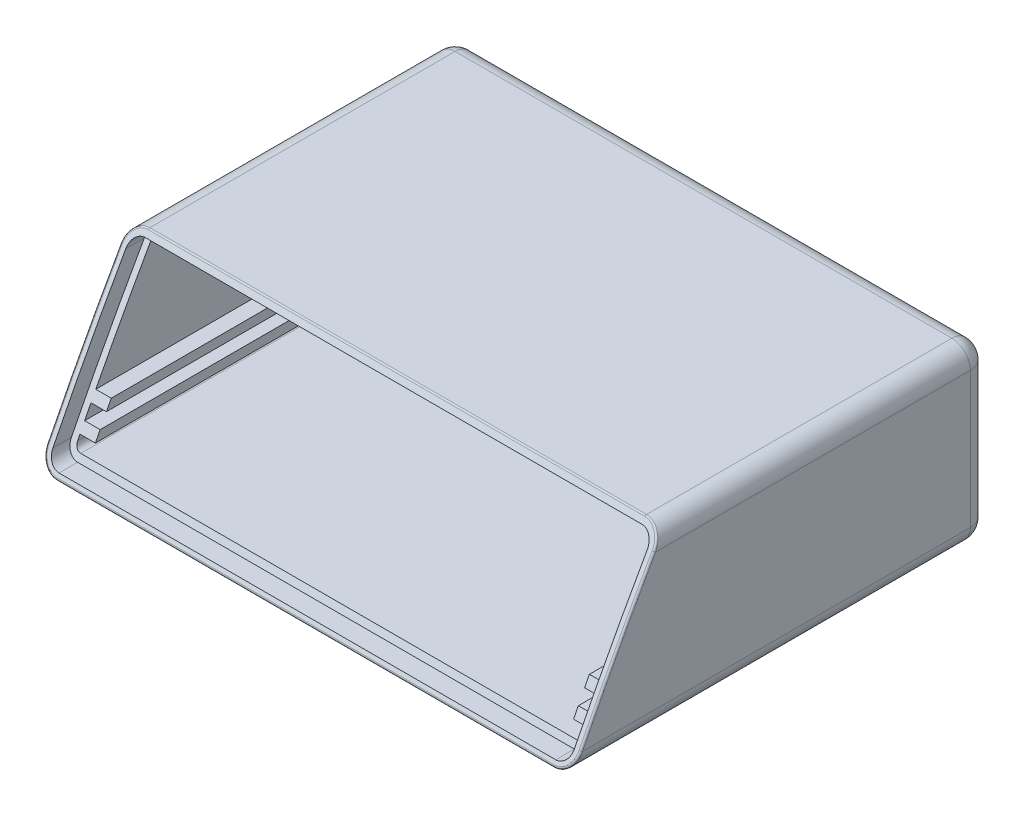
SolidWorks part; units mm, degrees
ref_plane "Front Plane" through (0, 0, 0) normal (0, 0, 1) x (1, 0, 0)
ref_plane "Top Plane" through (0, 0, 0) normal (0, 1, 0) x (1, 0, 0)
ref_plane "Right Plane" through (0, 0, 0) normal (1, 0, 0) x (0, 0, -1)
sketch "Sketch1" plane through (0, 0, 0) normal (0, 1, 0) x (1, 0, 0)
  line L1 (-43.14, -33.75) -> (43.14, -33.75)
  line L2 (-43.14, -33.75) -> (-43.14, 33.75)
  line L3 (-43.14, 33.75) -> (43.14, 33.75)
  line L4 (43.14, -33.75) -> (43.14, 33.75)
  line L5 (-43.14, -33.75) -> (43.14, 33.75) construction
  line L6 (-43.14, 33.75) -> (43.14, -33.75) construction
  point P0 (0, 0)
  dimension "D1" = 67.5
  dimension "D2" = 86.28
extrude "Boss-Extrude1" add sketch "Sketch1" along normal blind 28
fillet "Fillet1" radius 3 4 edges at (43.14, 28, 0) (43.14, 0, 0) (-43.14, 0, 0) (-43.14, 28, 0)
shell "Shell1" thickness 2
sketch "Sketch2" plane through (-43.14, 0, 0) normal (-1, 0, 0) x (0, 0, 1)
  line L0 (-33.75, 28) -> (33.75, 28) construction
  line L1 (18.75, 28) -> (33.75, 28)
  line L2 (33.75, 28) -> (33.75, 0)
  arc A0 (33.75, 0) -> (18.75, 28) centre (-392.2189, -210.1797) ccw
  dimension "D1" = 15
  dimension "D2" = 475
extrude "Cut-Extrude1" cut sketch "Sketch2" against normal through all
sketch "Sketch3" plane through (0, 0, -33.75) normal (0, 0, -1) x (-1, 0, 0)
  line L0 (-7.15, 18.7) -> (7.15, 18.7)
  line L1 (-6.95, 18.5) -> (6.95, 18.5) construction
  line L2 (-6.95, 18.5) -> (-6.95, 2.2) construction
  line L3 (-6.95, 2.2) -> (6.95, 2.2) construction
  line L4 (6.95, 18.5) -> (6.95, 2.2) construction
  line L5 (7.15, 18.7) -> (7.15, 2)
  line L6 (-7.15, 2) -> (7.15, 2)
  line L7 (-7.15, 18.7) -> (-7.15, 2)
  line L8 (27.25, 17.2) -> (38.3, 17.2)
  line L9 (27.45, 17) -> (38.1, 17) construction
  line L10 (27.45, 17) -> (27.45, 3.35) construction
  line L11 (27.45, 3.35) -> (38.1, 3.35) construction
  line L12 (38.1, 17) -> (38.1, 3.35) construction
  line L13 (38.3, 17.2) -> (38.3, 3.15)
  line L14 (27.25, 3.15) -> (38.3, 3.15)
  line L15 (27.25, 17.2) -> (27.25, 3.15)
  dimension "D1" = 0.2
  dimension "D2" = 0.2
extrude "Cut-Extrude2" cut sketch "Sketch3" against normal up to surface (2 mm away) up to face at (0, 14, -31.75)
fillet "Fillet2" radius 3 8 edges at (42.2613, 27.1213, -33.75) (43.14, 14, -33.75) (42.2613, 0.8787, -33.75) (0, 0, -33.75) (-42.2613, 0.8787, -33.75) (-43.14, 14, -33.75) (-42.2613, 27.1213, -33.75) (0, 28, -33.75)
sketch "Sketch4" plane through (0, 0, -31.75) normal (0, 0, 1) x (1, 0, 0)
  line L0 (-7.15, 2) -> (7.15, 2)
  line L1 (-7.15, 1) -> (7.15, 1)
  line L2 (7.15, 1) -> (40.14, 1)
  line L3 (42.14, 3) -> (42.14, 25)
  line L4 (40.14, 27) -> (-40.14, 27)
  line L5 (-42.14, 25) -> (-42.14, 3)
  line L6 (-40.14, 1) -> (-7.15, 1)
  line L8 (-7.15, 18.7) -> (7.15, 18.7)
  line L9 (7.15, 18.7) -> (7.15, 2)
  line L10 (7.15, 2) -> (40.14, 2)
  line L11 (41.14, 3) -> (41.14, 25)
  line L12 (40.14, 26) -> (-40.14, 26)
  line L13 (-41.14, 25) -> (-41.14, 3)
  line L14 (-40.14, 2) -> (-7.15, 2)
  line L15 (-7.15, 2) -> (-7.15, 18.7)
  line L18 (7.15, 2) -> (40.14, 2)
  line L19 (41.14, 3) -> (41.14, 25)
  line L20 (40.14, 26) -> (-40.14, 26)
  line L21 (-41.14, 25) -> (-41.14, 3)
  line L22 (-40.14, 2) -> (-7.15, 2)
  arc A0 (40.14, 1) -> (42.14, 3) centre (40.14, 3) ccw
  arc A1 (42.14, 25) -> (40.14, 27) centre (40.14, 25) ccw
  arc A2 (-40.14, 27) -> (-42.14, 25) centre (-40.14, 25) ccw
  arc A3 (-42.14, 3) -> (-40.14, 1) centre (-40.14, 3) ccw
  arc A4 (40.14, 2) -> (41.14, 3) centre (40.14, 3) ccw
  arc A5 (41.14, 25) -> (40.14, 26) centre (40.14, 25) ccw
  arc A6 (-40.14, 26) -> (-41.14, 25) centre (-40.14, 25) ccw
  arc A7 (-41.14, 3) -> (-40.14, 2) centre (-40.14, 3) ccw
  arc A8 (40.14, 2) -> (41.14, 3) centre (40.14, 3) ccw
  arc A9 (41.14, 25) -> (40.14, 26) centre (40.14, 25) ccw
  arc A10 (-40.14, 26) -> (-41.14, 25) centre (-40.14, 25) ccw
  arc A11 (-41.14, 3) -> (-40.14, 2) centre (-40.14, 3) ccw
  dimension "D1" = 0
  dimension "D2" = 1
extrude "Cut-Extrude3" cut sketch "Sketch4" against normal offset from surface (18.9934 mm away) 3 from offset 80
fillet "Fillet3" radius 0.3 8 edges at (42.123, 27.2511, 19.1831) (43.14, 14.0774, 26.5098) (41.8691, 0.5484, 33.479) (0, 0, 33.75) (-42.3299, 0.9496, 33.2802) (-43.14, 14.0774, 26.5098) (-41.8267, 27.4809, 19.0504) (0, 28, 18.75)
sketch "Sketch5" plane through (0, 0, -31.75) normal (0, 0, 1) x (1, 0, 0)
  line L0 (41.14, 25) -> (41.14, 3) construction
  line L1 (41.14, 5.25) -> (38.64, 5.25)
  line L2 (41.14, 5.25) -> (41.14, 3.75)
  line L3 (41.14, 3.75) -> (38.64, 3.75)
  line L4 (38.64, 5.25) -> (38.64, 3.75)
  line L5 (34.8894, 7.05) -> (40.64, 7.05) construction
  line L6 (41.14, 7.25) -> (38.64, 7.25)
  line L7 (41.14, 7.25) -> (41.14, 8.75)
  line L8 (41.14, 8.75) -> (38.64, 8.75)
  line L9 (38.64, 7.25) -> (38.64, 8.75)
  line L10 (-40.64, 7.05) -> (40.64, 7.05) construction
  line L11 (40.64, 5.45) -> (34.7752, 5.45) construction
  line L12 (-40.64, 5.45) -> (40.64, 5.45) construction
  line L13 (-41.14, 3) -> (-41.14, 25) construction
  line L14 (-41.14, 8.75) -> (-38.64, 8.75)
  line L15 (-41.14, 8.75) -> (-41.14, 7.25)
  line L16 (-41.14, 7.25) -> (-38.64, 7.25)
  line L17 (-38.64, 8.75) -> (-38.64, 7.25)
  line L19 (-41.14, 5.25) -> (-38.64, 5.25)
  line L20 (-41.14, 5.25) -> (-41.14, 3.75)
  line L21 (-41.14, 3.75) -> (-38.64, 3.75)
  line L22 (-38.64, 5.25) -> (-38.64, 3.75)
  dimension "D1" = 0.2
  dimension "D2" = 0.2
  dimension "D3" = 1.5
  dimension "D4" = 2.5
extrude "Boss-Extrude2" add sketch "Sketch5" along normal up to surface (59.8691 mm away)
